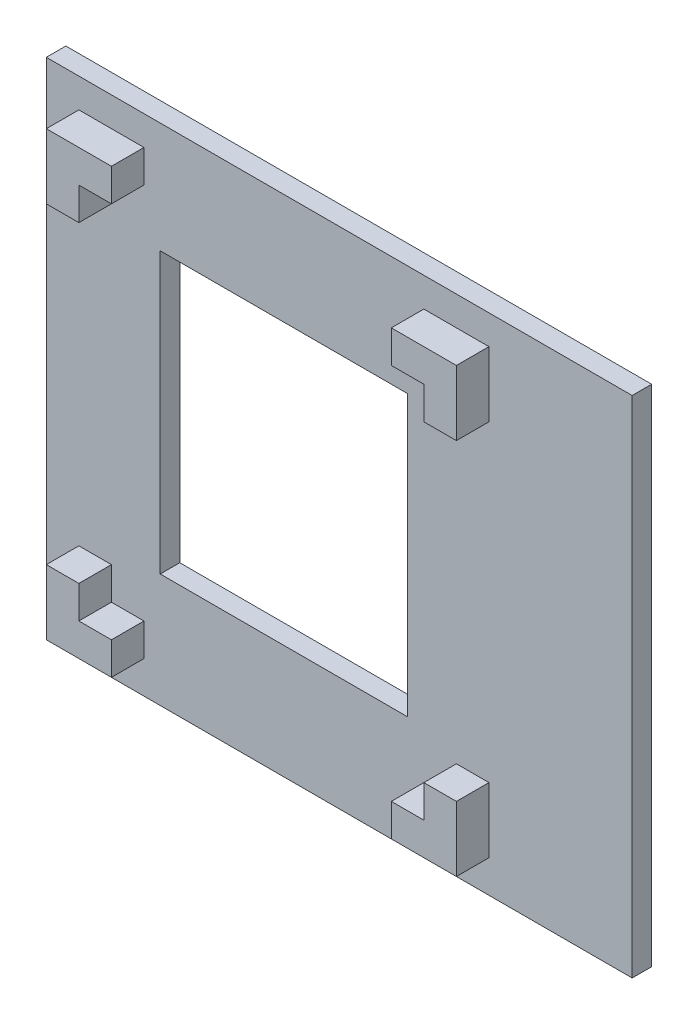
SolidWorks part; units mm, degrees
ref_plane "Front Plane" through (0, 0, 0) normal (0, 0, 1) x (1, 0, 0)
ref_plane "Top Plane" through (0, 0, 0) normal (0, 1, 0) x (1, 0, 0)
ref_plane "Right Plane" through (0, 0, 0) normal (1, 0, 0) x (0, 0, -1)
sketch "Sketch1" plane through (0, 0, 0) normal (0, 0, 1) x (1, 0, 0)
  line L0 (15, 10) -> (15, 68)
  line L1 (0, 0) -> (90, 0)
  line L2 (0, 0) -> (0, 77.5)
  line L3 (0, 77.5) -> (90, 77.5)
  line L4 (90, 0) -> (90, 77.5)
  line L5 (0, 0) -> (5, 0)
  line L6 (0, 0) -> (0, 5)
  line L7 (0, 5) -> (5, 5)
  line L8 (5, 0) -> (5, 5)
  line L9 (5, 5) -> (10, 5)
  line L10 (5, 5) -> (5, 15)
  line L11 (5, 15) -> (10, 15)
  line L12 (10, 5) -> (10, 15)
  line L13 (5, 5) -> (15, 5)
  line L14 (5, 5) -> (5, 10)
  line L15 (5, 10) -> (15, 10)
  line L16 (15, 5) -> (15, 10)
  line L17 (5, 73) -> (5, 77.5)
  line L18 (15, 68) -> (5, 68)
  line L19 (15, 68) -> (15, 73)
  line L20 (15, 73) -> (5, 73)
  line L21 (5, 68) -> (5, 73)
  line L22 (5, 73) -> (10, 73)
  line L23 (5, 73) -> (5, 63)
  line L24 (5, 63) -> (10, 63)
  line L25 (10, 73) -> (10, 63)
  line L26 (0, 65.1227) -> (5, 65.1227)
  line L27 (15, 10) -> (58, 10)
  line L28 (58, 10) -> (58, 68)
  line L29 (58, 10) -> (68, 10)
  line L30 (58, 10) -> (58, 5)
  line L31 (58, 5) -> (68, 5)
  line L32 (68, 10) -> (68, 5)
  line L33 (68, 5) -> (63, 5)
  line L34 (68, 5) -> (68, 15)
  line L35 (68, 15) -> (63, 15)
  line L36 (63, 5) -> (63, 15)
  line L38 (58, 68) -> (68, 68)
  line L39 (58, 68) -> (58, 73)
  line L40 (58, 73) -> (68, 73)
  line L41 (68, 68) -> (68, 73)
  line L42 (68, 73) -> (63, 73)
  line L43 (68, 73) -> (68, 63)
  line L44 (68, 63) -> (63, 63)
  line L45 (63, 73) -> (63, 63)
  dimension "D1" = 90
  dimension "D2" = 77.5
  dimension "D3" = 5
  dimension "D4" = 5
  dimension "D5" = 10
  dimension "D6" = 5
  dimension "D7" = 10
  dimension "D8" = 5
  dimension "D9" = 58
  dimension "D10" = 5
  dimension "D11" = 5
  dimension "D12" = 10
  dimension "D13" = 4.5
  dimension "D14" = 5
  dimension "D15" = 43
  dimension "D16" = 10
  dimension "D17" = 10
  dimension "D18" = 5
  dimension "D19" = 10
  dimension "D20" = 5
  dimension "D21" = 5
  dimension "D22" = 10
  dimension "D23" = 5
  dimension "D24" = 4.5
  dimension "D25" = 12.3773
extrude "Boss-Extrude2" add sketch "Sketch1" along normal blind 8 contours L15 L10 L9 L12 | L10 L15 L12 L11 | L13 L16 L15 L12 | L25 L20 L21 L18 | L25 L18 L23 L24 | L20 L25 L18 L19 | L45 L40 L39 L38 | L40 L45 L38 L41 | L38 L45 L44 L43 | L36 L29 L34 L35 | L36 L31 L32 L29 | L31 L36 L29 L30 region at (12.5, 7.5, 0) region at (60.5, 70.5, 0) region at (60.5, 7.5, 0) region at (12.5, 70.5, 0) region at (7.5, 12.5, 0) region at (7.5, 7.5, 0) region at (7.5, 65.5, 0) region at (7.5, 70.5, 0) region at (65.5, 12.5, 0) region at (65.5, 7.5, 0) region at (65.5, 70.5, 0) region at (65.5, 65.5, 0)
extrude "Boss-Extrude3" add sketch "Sketch1<4>" along normal blind 3 contours L1 L8 L7 L2 | L26 L2 L7 L10 L11 L12 L15 L0 L18 L25 L24 L23 | L45 L38 L29 L36 L35 L34 L32 L31 L30 L16 L13 L9 L8 L1 L4 L3 L17 L20 L19 L0 L39 L40 L41 L43 L44 | L2 L26 L23 L21 L17 L3 region at (7.4361, 37.5745, 0) region at (51.5035, 38.714, 0) region at (2.5, 71.3113, 0) region at (2.5, 2.5, 0)
sketch "Sketch1<4>" plane through (0, 0, 0) normal (0, 0, 1) x (1, 0, 0) same geometry as "Sketch1"
sketch "Sketch4" plane through (0, 0, 3) normal (0, 0, 1) x (1, 0, 0)
  line L1 (10, 68) -> (17.5, 68)
  line L2 (10, 68) -> (10, 60.5)
  line L3 (10, 60.5) -> (17.5, 60.5)
  line L4 (17.5, 68) -> (17.5, 60.5)
  line L5 (63, 10) -> (55.5, 10)
  line L6 (63, 10) -> (63, 17.5)
  line L7 (63, 17.5) -> (55.5, 17.5)
  line L8 (55.5, 10) -> (55.5, 17.5)
  line L9 (55.5, 17.5) -> (17.5, 17.5)
  line L10 (55.5, 17.5) -> (55.5, 60.5)
  line L11 (55.5, 60.5) -> (17.5, 60.5)
  line L12 (17.5, 17.5) -> (17.5, 60.5)
  dimension "D1" = 7.5
  dimension "D2" = 7.5
  dimension "D3" = 7.5
  dimension "D4" = 7.5
extrude "Cut-Extrude2" cut sketch "Sketch4" against normal blind 3 contours L12 L9 L10 L11 region at (36.5, 39, 3)
